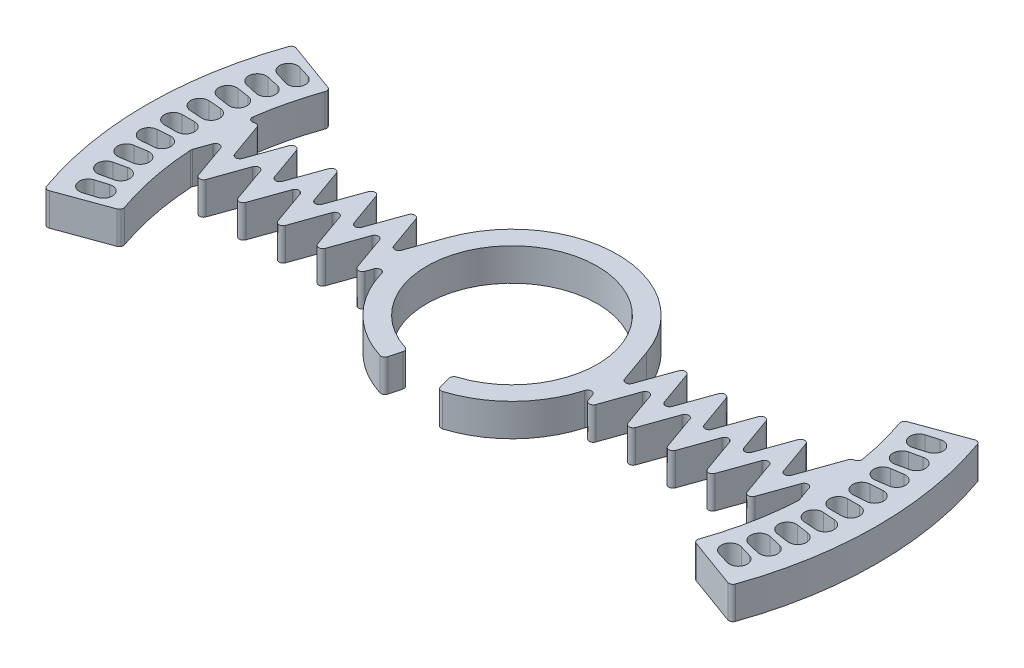
SolidWorks part; units mm, degrees
ref_plane "前视基准面" through (0, 0, 0) normal (0, 0, 1) x (1, 0, 0)
ref_plane "上视基准面" through (0, 0, 0) normal (0, 1, 0) x (1, 0, 0)
ref_plane "右视基准面" through (0, 0, 0) normal (1, 0, 0) x (0, 0, -1)
other "Configuration Table"
sketch "草图1" plane through (0, 0, 0) normal (0, 1, 0) x (1, 0, 0)
  line L0 (-1012, 0) -> (0, 0) construction
  line L1 (26, 0) -> (28.45, -6.8967) construction
  line L2 (28.45, -6.8967) -> (33.35, 6.8967) construction
  line L3 (33.35, 6.8967) -> (38.25, -6.8967) construction
  line L4 (38.25, -6.8967) -> (43.15, 6.8967) construction
  line L5 (43.15, 6.8967) -> (48.05, -6.8967) construction
  line L6 (48.05, -6.8967) -> (52.95, 6.8967) construction
  line L7 (52.95, 6.8967) -> (57.85, -6.8967) construction
  line L8 (57.85, -6.8967) -> (62.75, 6.8967) construction
  line L9 (62.75, 6.8967) -> (67.65, -6.8967) construction
  line L10 (67.65, -6.8967) -> (72.55, 6.8967) construction
  line L11 (72.55, 6.8967) -> (75, 0) construction
  line L12 (26, 0) -> (75, 0) construction
  line L13 (5.4352, -20.2844) -> (6.7293, -25.1141)
  line L14 (6.7293, -25.1141) -> (5.4352, -20.2844)
  line L15 (-5.4352, -20.2844) -> (-6.7293, -25.1141)
  line L16 (0, 0) -> (0, -50000) construction
  line L17 (0, 0) -> (-5.4352, -20.2844) construction
  line L18 (0, 0) -> (5.4352, -20.2844) construction
  line L19 (5.4352, -20.2844) -> (0, 0) construction
  line L20 (84.5723, -30.7818) -> (70.4769, -25.6515)
  line L21 (84.5723, 30.7818) -> (70.4769, 25.6515)
  line L22 (-26, 0) -> (-75, 0) construction
  line L23 (-72.55, 6.8967) -> (-75, 0) construction
  line L24 (-67.65, -6.8967) -> (-72.55, 6.8967) construction
  line L29 (-62.75, 6.8967) -> (-67.65, -6.8967) construction
  line L30 (-57.85, -6.8967) -> (-62.75, 6.8967) construction
  line L31 (25.7317, -3.7257) -> (28.45, -11.3777)
  line L32 (28.45, -11.3777) -> (33.35, 2.4157)
  line L33 (33.35, 2.4157) -> (38.25, -11.3777)
  line L34 (38.25, -11.3777) -> (43.15, 2.4157)
  line L35 (43.15, 2.4157) -> (48.05, -11.3777)
  line L36 (48.05, -11.3777) -> (52.95, 2.4157)
  line L37 (52.95, 2.4157) -> (57.85, -11.3777)
  line L38 (57.85, -11.3777) -> (62.75, 2.4157)
  line L39 (62.75, 2.4157) -> (67.65, -11.3777)
  line L40 (67.65, -11.3777) -> (72.55, 2.4157)
  line L41 (72.55, 2.4157) -> (74.8847, -4.1565)
  line L42 (24.5, 8.7034) -> (28.45, -2.4157)
  line L43 (28.45, -2.4157) -> (33.35, 11.3777)
  line L44 (33.35, 11.3777) -> (38.25, -2.4157)
  line L45 (38.25, -2.4157) -> (43.15, 11.3777)
  line L46 (43.15, 11.3777) -> (48.05, -2.4157)
  line L47 (48.05, -2.4157) -> (52.95, 11.3777)
  line L48 (52.95, 11.3777) -> (57.85, -2.4157)
  line L49 (57.85, -2.4157) -> (62.75, 11.3777)
  line L50 (62.75, 11.3777) -> (67.65, -2.4157)
  line L51 (67.65, -2.4157) -> (72.55, 11.3777)
  line L52 (72.55, 11.3777) -> (74.8372, 4.9393)
  line L53 (27.4135, 0.5021) -> (28.45, -2.4157) construction
  line L54 (72.55, 2.4157) -> (73.5865, -0.5021) construction
  line L55 (-52.95, 6.8967) -> (-57.85, -6.8967) construction
  line L56 (-48.05, -6.8967) -> (-52.95, 6.8967) construction
  line L57 (-43.15, 6.8967) -> (-48.05, -6.8967) construction
  line L58 (-38.25, -6.8967) -> (-43.15, 6.8967) construction
  line L59 (-33.35, 6.8967) -> (-38.25, -6.8967) construction
  line L60 (-28.45, -6.8967) -> (-33.35, 6.8967) construction
  line L61 (-26, 0) -> (-28.45, -6.8967) construction
  line L62 (1012, 0) -> (0, 0) construction
  line L63 (-72.55, 11.3777) -> (-74.8372, 4.9393)
  line L64 (-67.65, -2.4157) -> (-72.55, 11.3777)
  line L65 (-62.75, 11.3777) -> (-67.65, -2.4157)
  line L67 (-50000, 0) -> (50000, 0) construction
  line L70 (-57.85, -2.4157) -> (-62.75, 11.3777)
  line L71 (-52.95, 11.3777) -> (-57.85, -2.4157)
  line L72 (24.5865, -0.5021) -> (28.45, -11.3777) construction
  line L73 (-48.05, -2.4157) -> (-52.95, 11.3777)
  line L74 (72.55, 11.3777) -> (76.4135, 0.5021) construction
  line L75 (-43.15, 11.3777) -> (-48.05, -2.4157)
  line L76 (-38.25, -2.4157) -> (-43.15, 11.3777)
  line L77 (-33.35, 11.3777) -> (-38.25, -2.4157)
  line L78 (-28.45, -2.4157) -> (-33.35, 11.3777)
  line L79 (-24.5, 8.7034) -> (-28.45, -2.4157)
  line L80 (-72.55, 2.4157) -> (-74.8847, -4.1565)
  line L81 (-67.65, -11.3777) -> (-72.55, 2.4157)
  line L82 (-62.75, 2.4157) -> (-67.65, -11.3777)
  line L83 (-57.85, -11.3777) -> (-62.75, 2.4157)
  line L84 (-52.95, 2.4157) -> (-57.85, -11.3777)
  line L85 (-48.05, -11.3777) -> (-52.95, 2.4157)
  line L86 (-43.15, 2.4157) -> (-48.05, -11.3777)
  line L87 (-38.25, -11.3777) -> (-43.15, 2.4157)
  line L88 (-33.35, 2.4157) -> (-38.25, -11.3777)
  line L89 (-28.45, -11.3777) -> (-33.35, 2.4157)
  line L90 (-25.7317, -3.7257) -> (-28.45, -11.3777)
  line L91 (-84.5723, 30.7818) -> (-70.4769, 25.6515)
  line L92 (-84.5723, -30.7818) -> (-70.4769, -25.6515)
  arc A2 (0, 90) -> (-90, 0) centre (0, 0) ccw construction
  arc A4 (0, 75) -> (-75, 0) centre (0, 0) ccw construction
  arc A5 (6.7293, -25.1141) -> (25.7317, -3.7257) centre (0, 0) ccw
  arc A8 (5.4352, -20.2844) -> (-5.4352, -20.2844) centre (0, 0) ccw
  arc A10 (-6.7293, -25.1141) -> (0, -26) centre (0, 0) ccw construction
  arc A12 (-5.4352, -20.2844) -> (0, -21) centre (0, 0) ccw construction
  arc A13 (0, -26) -> (6.7293, -25.1141) centre (0, 0) ccw construction
  arc A14 (0, -21) -> (5.4352, -20.2844) centre (0, 0) ccw construction
  arc A15 (26, 0) -> (24.5, 8.7034) centre (0, 0) ccw construction
  arc A16 (24.5, 8.7034) -> (-24.5, 8.7034) centre (0, 0) ccw
  arc A17 (25.7317, -3.7257) -> (26, 0) centre (0, 0) ccw construction
  arc A18 (70.4769, 25.6515) -> (-70.4769, 25.6515) centre (0, 0) ccw construction
  arc A19 (84.5723, 30.7818) -> (-84.5723, 30.7818) centre (0, 0) ccw construction
  arc A20 (-84.5723, -30.7818) -> (84.5723, -30.7818) centre (0, 0) ccw construction
  arc A21 (84.5723, -30.7818) -> (84.5723, 30.7818) centre (0, 0) ccw
  arc A22 (-70.4769, -25.6515) -> (70.4769, -25.6515) centre (0, 0) ccw construction
  arc A23 (70.4769, -25.6515) -> (74.8847, -4.1565) centre (0, 0) ccw
  arc A24 (-75, 0) -> (0, -75) centre (0, 0) ccw construction
  arc A25 (-90, 0) -> (0, -90) centre (0, 0) ccw construction
  arc A26 (74.8847, -4.1565) -> (75, 0) centre (0, 0) ccw construction
  arc A27 (74.8372, 4.9393) -> (70.4769, 25.6515) centre (0, 0) ccw
  arc A28 (75, 0) -> (74.8372, 4.9393) centre (0, 0) ccw construction
  arc A29 (-75, 0) -> (-74.8372, 4.9393) centre (0, 0) cw construction
  arc A30 (-74.8847, -4.1565) -> (-75, 0) centre (0, 0) cw construction
  arc A31 (-74.8372, 4.9393) -> (-70.4769, 25.6515) centre (0, 0) cw
  arc A32 (-70.4769, -25.6515) -> (-74.8847, -4.1565) centre (0, 0) cw
  arc A33 (-84.5723, -30.7818) -> (-84.5723, 30.7818) centre (0, 0) cw
  arc A34 (-26, 0) -> (-25.7317, -3.7257) centre (0, 0) ccw construction
  arc A35 (-25.7317, -3.7257) -> (-6.7293, -25.1141) centre (0, 0) ccw
  arc A36 (-24.5, 8.7034) -> (-26, 0) centre (0, 0) ccw construction
  point P10 (30.9, 0)
  dimension "D1" = 150
  dimension "D2" = 52
  dimension "D3" = 180
  dimension "D4" = 42
  dimension "D5" = 15
  dimension "D6" = 15
  dimension "D7" = 20
  dimension "D10" = 20
  dimension "D8" = 1.5
  dimension "D9" = 1.5
extrude "凸台-拉伸1" add sketch "草图1" along normal blind 8 contours A27 L52 L51 L50 L49 L48 L47 L46 L45 L44 L43 L42 A16 L15 A8 L13 A5 L31 L32 L33 L34 L35 L36 L37 L38 L39 L40 L41 A23 L20 A21 L21 region at (0, 0, -22.9024)
sketch "草图2" plane through (0, 8, 0) normal (0, 1, 0) x (1, 0, 0)
  line L0 (0, 0) -> (122.9556, 0) construction
  line L1 (0, 0) -> (0, 50000) construction
  line L2 (-83.5, 0) -> (-80.5, 0) construction
  line L3 (-83.5, -2.2) -> (-80.5, -2.2)
  line L4 (-83.5, 2.2) -> (-80.5, 2.2)
  line L5 (83.5, 2.2) -> (80.5, 2.2)
  line L6 (83.5, -2.2) -> (80.5, -2.2)
  line L7 (-83.4299, 4.0669) -> (-80.4384, 3.842)
  line L8 (-83.1, 8.4545) -> (-80.1085, 8.2296)
  line L9 (-82.8901, 10.3109) -> (-79.9239, 9.8623)
  line L10 (-82.2322, 14.6615) -> (-79.2659, 14.2129)
  line L11 (-81.8837, 16.4969) -> (-78.9594, 15.8272)
  line L12 (-80.9014, 20.7859) -> (-77.9771, 20.1161)
  line L13 (-80.4163, 22.59) -> (-77.5505, 21.7029)
  line L14 (-79.1152, 26.7932) -> (-76.2494, 25.9061)
  line L15 (0, 0) -> (-80.5, 0) construction
  line L16 (0, 0) -> (-80.2734, 6.0358) construction
  line L17 (-83.1, -8.4545) -> (-80.1085, -8.2296)
  line L18 (-83.4299, -4.0669) -> (-80.4384, -3.842)
  line L19 (-82.2322, -14.6615) -> (-79.2659, -14.2129)
  line L20 (-82.8901, -10.3109) -> (-79.9239, -9.8623)
  line L21 (-80.9014, -20.7859) -> (-77.9771, -20.1161)
  line L22 (-81.8837, -16.4969) -> (-78.9594, -15.8272)
  line L23 (-79.1152, -26.7932) -> (-76.2494, -25.9061)
  line L24 (-80.4163, -22.59) -> (-77.5505, -21.7029)
  line L25 (0, 0) -> (-80.5, 0) construction
  line L26 (0, 0) -> (-80.2734, -6.0358) construction
  line L27 (83.1146, -8.3095) -> (80.1227, -8.0898)
  line L28 (83.4369, -3.9213) -> (80.4449, -3.7016)
  line L29 (82.2829, -14.3743) -> (79.315, -13.9361)
  line L30 (82.9256, -10.0215) -> (79.9578, -9.5833)
  line L31 (81.0091, -20.362) -> (78.0814, -19.7075)
  line L32 (81.969, -16.0679) -> (79.0412, -15.4135)
  line L33 (79.3003, -26.2403) -> (76.4283, -25.3732)
  line L34 (80.572, -22.0281) -> (77.7001, -21.161)
  line L35 (0, 0) -> (80.5, 0) construction
  line L36 (0, 0) -> (80.2838, -5.8957) construction
  line L37 (83.4369, 3.9213) -> (80.4449, 3.7016)
  line L38 (83.1146, 8.3095) -> (80.1227, 8.0898)
  line L39 (82.9256, 10.0215) -> (79.9578, 9.5833)
  line L40 (82.2829, 14.3743) -> (79.315, 13.9361)
  line L41 (81.969, 16.0679) -> (79.0412, 15.4135)
  line L42 (81.0091, 20.362) -> (78.0814, 19.7075)
  line L43 (80.572, 22.0281) -> (77.7001, 21.161)
  line L44 (79.3003, 26.2403) -> (76.4283, 25.3732)
  line L45 (0, 0) -> (80.5, 0) construction
  line L46 (0, 0) -> (80.2838, 5.8957) construction
  circle A0 centre (0, 0) radius 82 construction
  arc A1 (-83.5, -2.2) -> (-83.5, 2.2) centre (-83.5, 0) cw
  arc A2 (-80.5, -2.2) -> (-80.5, 2.2) centre (-80.5, 0) ccw
  arc A3 (83.5, -2.2) -> (83.5, 2.2) centre (83.5, 0) ccw
  arc A4 (80.5, -2.2) -> (80.5, 2.2) centre (80.5, 0) cw
  arc A5 (-80.4384, 3.842) -> (-80.1085, 8.2296) centre (-80.2734, 6.0358) ccw
  arc A6 (-83.4299, 4.0669) -> (-83.1, 8.4545) centre (-83.265, 6.2607) cw
  arc A7 (-79.9239, 9.8623) -> (-79.2659, 14.2129) centre (-79.5949, 12.0376) ccw
  arc A8 (-82.8901, 10.3109) -> (-82.2322, 14.6615) centre (-82.5612, 12.4862) cw
  arc A9 (-78.9594, 15.8272) -> (-77.9771, 20.1161) centre (-78.4683, 17.9716) ccw
  arc A10 (-81.8837, 16.4969) -> (-80.9014, 20.7859) centre (-81.3926, 18.6414) cw
  arc A11 (-77.5505, 21.7029) -> (-76.2494, 25.9061) centre (-76.8999, 23.8045) ccw
  arc A12 (-80.4163, 22.59) -> (-79.1152, 26.7932) centre (-79.7657, 24.6916) cw
  arc A13 (-80.1085, -8.2296) -> (-80.4384, -3.842) centre (-80.2734, -6.0358) ccw
  arc A14 (-83.1, -8.4545) -> (-83.4299, -4.0669) centre (-83.265, -6.2607) cw
  arc A15 (-79.2659, -14.2129) -> (-79.9239, -9.8623) centre (-79.5949, -12.0376) ccw
  arc A16 (-82.2322, -14.6615) -> (-82.8901, -10.3109) centre (-82.5612, -12.4862) cw
  arc A17 (-77.9771, -20.1161) -> (-78.9594, -15.8272) centre (-78.4683, -17.9716) ccw
  arc A18 (-80.9014, -20.7859) -> (-81.8837, -16.4969) centre (-81.3926, -18.6414) cw
  arc A19 (-76.2494, -25.9061) -> (-77.5505, -21.7029) centre (-76.8999, -23.8045) ccw
  arc A20 (-79.1152, -26.7932) -> (-80.4163, -22.59) centre (-79.7657, -24.6916) cw
  arc A21 (83.1146, -8.3095) -> (83.4369, -3.9213) centre (83.2758, -6.1154) ccw
  arc A22 (80.1227, -8.0898) -> (80.4449, -3.7016) centre (80.2838, -5.8957) cw
  arc A23 (82.2829, -14.3743) -> (82.9256, -10.0215) centre (82.6042, -12.1979) ccw
  arc A24 (79.315, -13.9361) -> (79.9578, -9.5833) centre (79.6364, -11.7597) cw
  arc A25 (81.0091, -20.362) -> (81.969, -16.0679) centre (81.489, -18.215) ccw
  arc A26 (78.0814, -19.7075) -> (79.0412, -15.4135) centre (78.5613, -17.5605) cw
  arc A27 (79.3003, -26.2403) -> (80.572, -22.0281) centre (79.9362, -24.1342) ccw
  arc A28 (76.4283, -25.3732) -> (77.7001, -21.161) centre (77.0642, -23.2671) cw
  arc A29 (83.4369, 3.9213) -> (83.1146, 8.3095) centre (83.2758, 6.1154) ccw
  arc A30 (80.4449, 3.7016) -> (80.1227, 8.0898) centre (80.2838, 5.8957) cw
  arc A31 (82.9256, 10.0215) -> (82.2829, 14.3743) centre (82.6042, 12.1979) ccw
  arc A32 (79.9578, 9.5833) -> (79.315, 13.9361) centre (79.6364, 11.7597) cw
  arc A33 (81.969, 16.0679) -> (81.0091, 20.362) centre (81.489, 18.215) ccw
  arc A34 (79.0412, 15.4135) -> (78.0814, 19.7075) centre (78.5613, 17.5605) cw
  arc A35 (80.572, 22.0281) -> (79.3003, 26.2403) centre (79.9362, 24.1342) ccw
  arc A36 (77.7001, 21.161) -> (76.4283, 25.3732) centre (77.0642, 23.2671) cw
  point P10 (-82, 0)
  dimension "D1" = 164
  dimension "D2" = 3
  dimension "D3" = 2.2
  dimension "D6" = 4.3
  dimension "D8" = 4.3
  dimension "D10" = 4.2
  dimension "D12" = 4.2
  dimension "D4" = 2.2
  dimension "D5" = 5
  dimension "D7" = 5
  dimension "D9" = 5
  dimension "D11" = 5
extrude "切除-拉伸1" cut sketch "草图2" against normal through all
fillet "圆角7" radius 1 1 edges at (-28.45, 4, 11.3777)
fillet "圆角8" radius 1 1 edges at (74.8372, 4, -4.9393)
fillet "圆角9" radius 1 29 edges at (72.55, 4, -11.3777) (-70.4769, 4, -25.6515) (-52.95, 4, -11.3777) (-57.85, 4, 2.4157) (-62.75, 4, -11.3777) (-67.65, 4, 2.4157) (-72.55, 4, -11.3777) (70.4769, 4, -25.6515) (74.8847, 4, 4.1565) (84.5723, 4, 30.7818) (84.5723, 4, -30.7818) (70.4769, 4, 25.6515) (72.55, 4, -2.4157) (67.65, 4, 11.3777) (62.75, 4, -2.4157) (28.45, 4, 2.4157) (-28.45, 4, 2.4157) (-33.35, 4, -11.3777) (-38.25, 4, 2.4157) (-43.15, 4, -11.3777) (-48.05, 4, 2.4157) (33.35, 4, -11.3777) (38.25, 4, 2.4157) (43.15, 4, -11.3777) (48.05, 4, 2.4157) (52.95, 4, -11.3777) (57.85, 4, 2.4157) (62.75, 4, -11.3777) (67.65, 4, 2.4157)
fillet "圆角10" radius 1 27 edges at (-74.8372, 4, -4.9393) (-33.35, 4, -2.4157) (-38.25, 4, 11.3777) (-43.15, 4, -2.4157) (-48.05, 4, 11.3777) (-6.7293, 4, 25.1141) (5.4352, 4, 20.2844) (-5.4352, 4, 20.2844) (6.7293, 4, 25.1141) (-25.7317, 4, 3.7257) (-70.4769, 4, 25.6515) (-84.5723, 4, 30.7818) (-52.95, 4, -2.4157) (-57.85, 4, 11.3777) (-62.75, 4, -2.4157) (-67.65, 4, 11.3777) (-72.55, 4, -2.4157) (-74.8847, 4, 4.1565) (57.85, 4, 11.3777) (52.95, 4, -2.4157) (48.05, 4, 11.3777) (43.15, 4, -2.4157) (38.25, 4, 11.3777) (33.35, 4, -2.4157) (28.45, 4, 11.3777) (25.7317, 4, 3.7257) (-84.5723, 4, -30.7818)
